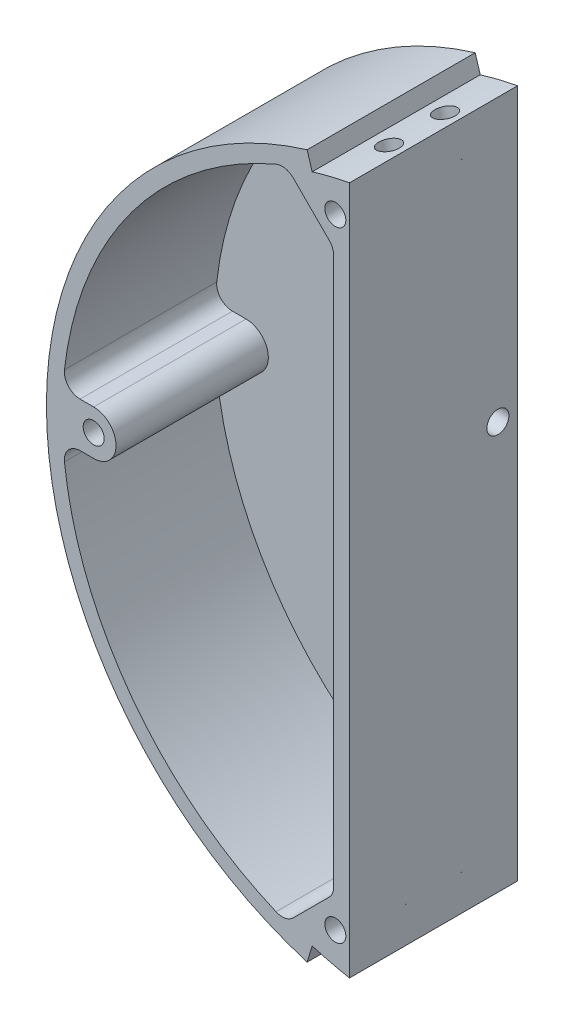
SolidWorks part; units mm, degrees
ref_plane "Front Plane" through (0, 0, 0) normal (0, 0, 1) x (1, 0, 0)
ref_plane "Top Plane" through (0, 0, 0) normal (0, 1, 0) x (1, 0, 0)
ref_plane "Right Plane" through (0, 0, 0) normal (1, 0, 0) x (0, 0, -1)
sketch "Sketch1" plane through (0, 0, 0) normal (0, 0, 1) x (1, 0, 0)
  line L0 (-12.3, -68.9109) -> (-12.3, 68.9109)
  line L1 (-15, 59) -> (-15, -59) construction
  line L5 (-61, 0) -> (0, 0) construction
  circle A2 centre (-15, 59) radius 1.25
  circle A4 centre (-61, 0) radius 1.25
  circle A5 centre (-15, -59) radius 1.25
  arc A6 (-12.3, 68.9109) -> (-12.3, -68.9109) centre (0, 0) ccw
  circle A7 centre (0, 0) radius 65.5 construction
  circle A8 centre (-15, 59) radius 3 construction
  circle A9 centre (-61, 0) radius 3 construction
  circle A10 centre (-15, -59) radius 3 construction
  point P6 (-15, 0)
  dimension "D2" = 2.5
  dimension "D6" = 118
  dimension "D7" = 131
  dimension "D8" = 2.5
  dimension "D4" = 70
  dimension "D3" = 2.5
  dimension "D10" = 6
  dimension "D1" = 12.3
  dimension "D5" = 15
  dimension "D9" = 61
extrude "Boss-Extrude2" add sketch "Sketch1" along normal blind 32
shell "Shell1" thickness 3 removed face at (-13.75, 59, 32)
sketch "Sketch10" plane through (0, 0, 3) normal (0, 0, 1) x (1, 0, 0)
  line L0 (-15.3, 53.2896) -> (-24.4068, 62.3964)
  line L1 (-15.3, -54.7606) -> (-15.3, 54.7606) construction
  line L2 (-15.3, -53.2896) -> (-24.4068, -62.3964)
  line L3 (-15.3, -54.7606) -> (-15.3, 54.7606) construction
  line L4 (-15.3, 65.2297) -> (-15.3, 60.2135)
  line L5 (-15.3, 57.7865) -> (-15.3, 53.2896)
  line L6 (-15.3, 63.2394) -> (-15.3, 65.2297) construction
  line L7 (-15.3, -65.2297) -> (-15.3, -60.2135)
  line L8 (-15.3, -57.7865) -> (-15.3, -53.2896)
  line L9 (-61, -4.25) -> (-63.588, -4.25)
  line L10 (-61, 4.25) -> (-63.588, 4.25)
  arc A0 (-24.4068, 62.3964) -> (-15.3, 65.2297) centre (0, 0) cw
  arc A1 (-63.588, -4.25) -> (-66.5687, -7.5898) centre (-63.588, -7.25) ccw
  arc A2 (-15.3, 65.2297) -> (-15.3, -65.2297) centre (0, 0) ccw construction
  arc A3 (-15.3, 65.2297) -> (-15.3, -65.2297) centre (0, 0) ccw construction
  arc A4 (-15.3, -54.7606) -> (-15.3, -63.2394) centre (-15, -59) ccw construction
  arc A5 (-15.3, 63.2394) -> (-15.3, 54.7606) centre (-15, 59) ccw construction
  arc A6 (-15.3, -65.2297) -> (-24.4068, -62.3964) centre (0, 0) cw
  circle A7 centre (-15, 59) radius 1.25 construction
  arc A8 (-15.3, 60.2135) -> (-15.3, 57.7865) centre (-15, 59) ccw
  circle A9 centre (-15, -59) radius 1.25 construction
  arc A10 (-15.3, -60.2135) -> (-15.2655, -57.7785) centre (-15, -59) cw
  arc A11 (-61, 4.25) -> (-61, -4.25) centre (-61, 0) cw
  circle A12 centre (-61, 0) radius 4.25 construction
  circle A13 centre (-61, 0) radius 4.25 construction
  arc A14 (-63.588, 4.25) -> (-66.5687, 7.5898) centre (-63.588, 7.25) cw
  arc A15 (-66.5687, 7.5898) -> (-66.5687, -7.5898) centre (0, 0) ccw
  circle A16 centre (-61, 0) radius 1.25
  point P57 (-66.8651, 4.25)
  line M8 (-15.3, 63.2394) -> (-15.3, 65.2297)
  arc M9 (-15.3, 65.2297) -> (-15.3, -65.2297) centre (0, 0) ccw
  line M10 (-15.3, -65.2297) -> (-15.3, -63.2394)
  arc M11 (-15.3, -63.2394) -> (-15.3, -54.7606) centre (-15, -59) cw
  line M12 (-15.3, -54.7606) -> (-15.3, 54.7606)
  arc M13 (-15.3, 54.7606) -> (-15.3, 63.2394) centre (-15, 59) cw
  circle M14 centre (-61, 0) radius 4.25
  dimension "D3" = 3
  dimension "D1" = 135
  dimension "D2" = 135
extrude "Boss-Extrude6" add sketch "Sketch10" along normal up to surface (29 mm away) contours L10 A14 A1 L9 M9 M14 | A16 M14 | L7 A10 L8 M11 | L2 M11 M9 M10 | L0 M13 M8 M9 | A8 L4 L5 M13 | L2 M12 M11 | L0 M12 M13 region at (-16.0191, 54.4613, 3) region at (-17.0571, 59, 3) region at (-19.7689, 61.9404, 3) region at (-16.0191, -54.4613, 3) region at (-19.7689, -61.9404, 3) region at (-17.0571, -59, 3) region at (-65.581, 0, 3) region at (-58.0798, 2.9202, 3) up to face at (-25.2333, 0, 32)
fillet "Fillet1" radius 3 4 edges at (-24.4068, -62.3964, 17.5) (-15.3, -53.2896, 17.5) (-15.3, 53.2896, 17.5) (-24.4068, 62.3964, 17.5)
sketch "Sketch11" plane through (-12.3, 0, 0) normal (1, 0, 0) x (0, 0, -1)
  line L2 (0, -68.9109) -> (0, 68.9109) construction
  circle A0 centre (-3.75, 12) radius 2.1
  circle A1 centre (-3.75, 12) radius 0.75 construction
  dimension "D1" = 4.2
  dimension "D3" = 1.5
  dimension "D4" = 3
  dimension "D2" = 12
extrude "Cut-Extrude4" cut sketch "Sketch11" against normal blind 5
sketch "Sketch12" plane through (0, 0, 32) normal (0, 0, 1) x (1, 0, 0)
  circle A0 centre (-15, -59) radius 2
  circle A1 centre (-61, 0) radius 2
  circle A2 centre (-15, 59) radius 2
  dimension "D1" = 4
extrude "Thread insert holes" cut sketch "Sketch12" against normal blind 4.78
sketch "Sketch13" plane through (0, 0, 0) normal (0, 0, -1) x (-1, 0, 0)
  circle A0 centre (15, 59) radius 2
  circle A1 centre (61, 0) radius 2
  circle A2 centre (15, -59) radius 2
  dimension "D1" = 4
extrude "Cut-Extrude6" cut sketch "Sketch13" against normal blind 4.78
sketch "Sketch14" plane through (0, 0, 0) normal (0, 0, 1) x (1, 0, 0)
  line L0 (-12.3, -68.9109) -> (-12.3, 68.9109) construction
  line L1 (-20.3654, -66.972) -> (0, 0) construction
  line L2 (0, 0) -> (-20.3654, 66.972) construction
  line L3 (-19.4053, -63.8148) -> (-20.3654, -66.972)
  line L4 (-19.4053, 63.8148) -> (-20.3654, 66.972)
  line L5 (-12.3, 65.5561) -> (-12.3, 68.9109)
  line L6 (-12.3, -65.5561) -> (-12.3, -68.9109)
  arc A0 (-12.3, 68.9109) -> (-20.3654, 66.972) centre (0, 0) ccw
  arc A1 (-12.3, -68.9109) -> (-20.3654, -66.972) centre (0, 0) cw
  arc A2 (-12.3, -65.5561) -> (-19.4053, -63.8148) centre (0, 0) cw
  arc A3 (-12.3, 65.5561) -> (-19.4053, 63.8148) centre (0, 0) ccw
  dimension "D3" = 3.3
  dimension "D4" = 3.3
  dimension "D1" = 8.3
  dimension "D2" = 8.3
extrude "Cut-Extrude7" cut sketch "Sketch14" along normal blind 32
sketch "Sketch15" plane through (0, 0, 0) normal (0, 0, 1) x (1, 0, 0)
  line L0 (-12.3, -65.5561) -> (-12.3, 65.5561) construction
  arc A0 (-12.3, -68.9109) -> (-20.0782, -67.0587) centre (0, 0) cw
  arc A1 (-12.3, 68.9109) -> (-20.0782, 67.0587) centre (0, 0) ccw
  circle A2 centre (0, 0) radius 70 construction
  point P11 (-16.2155, 68.0959)
  point P13 (-16.2155, -68.0959)
  dimension "D2" = 140
  dimension "D1" = 8
  dimension "D3" = 8
sketch3d "3DSketch1"
  line L0 (-16.2155, -68.0959, 0) -> (-16.2155, -68.0959, 32)
  line L2 (-16.2155, 68.0959, 0) -> (-16.2155, 68.0959, 32)
  arc A0 (-12.3, 68.9109, 0) -> (-20.0782, 67.0587, 0) centre (0, 0, 0) ccw construction
  point P9 (0, 0, 70)
ref_plane "Plane1" through (-16.2155, 68.0959, 0) normal (-0.2317, 0.9728, 0) x (0.9728, 0.2317, 0)
ref_plane "Plane2" through (-16.2155, -68.0959, 0) normal (-0.2317, -0.9728, 0) x (-0.9728, 0.2317, 0)
sketch "Sketch16" plane through (-16.2155, 68.0959, 0) normal (-0.2317, 0.9728, 0) x (0.9728, 0.2317, 0)
  line L0 (0, 0) -> (0, -32) construction
  circle A0 centre (0, -10.6667) radius 1.65
  circle A1 centre (0, -21.3333) radius 1.65
  dimension "D1" = 10.6667
  dimension "D3" = 3.3
  dimension "D2" = 21.3333
extrude "Cut-Extrude8" cut sketch "Sketch16" against normal blind 10
sketch "Sketch17" plane through (-16.2155, -68.0959, 0) normal (-0.2317, -0.9728, 0) x (-0.9728, 0.2317, 0)
  line L0 (0, 0) -> (0, -32) construction
  circle A0 centre (0, -10.6667) radius 1.65
  circle A1 centre (0, -21.3333) radius 1.65
  dimension "D1" = 10.6667
  dimension "D2" = 21.3333
  dimension "D3" = 3.3
extrude "Cut-Extrude9" cut sketch "Sketch17" against normal blind 10
sketch "Sketch18" plane through (-16.2155, 68.0959, 0) normal (-0.2317, 0.9728, 0) x (0.9728, 0.2317, 0)
  circle A0 centre (0, -10.6667) radius 2
  circle A1 centre (0, -21.3333) radius 2
  dimension "D1" = 4
  dimension "D2" = 4
extrude "Cut-Extrude10" cut sketch "Sketch18" against normal blind 8
sketch "Sketch19" plane through (-16.2155, -68.0959, 0) normal (-0.2317, -0.9728, 0) x (-0.9728, 0.2317, 0)
  circle A0 centre (0, -10.6667) radius 2
  circle A1 centre (0, -21.3333) radius 2
  dimension "D1" = 4
extrude "Cut-Extrude11" cut sketch "Sketch19" against normal blind 8
